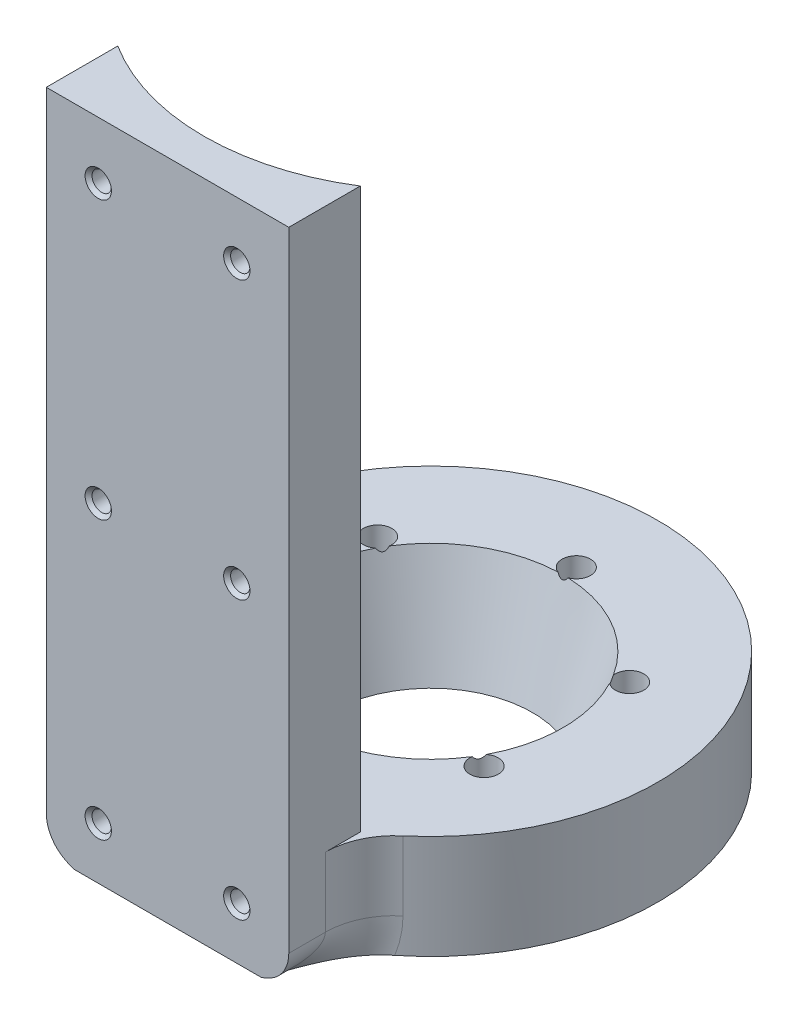
SolidWorks part; units mm, degrees
ref_plane "Front Plane" through (0, 0, 0) normal (0, 0, 1) x (1, 0, 0)
ref_plane "Top Plane" through (0, 0, 0) normal (0, 1, 0) x (1, 0, 0)
ref_plane "Right Plane" through (0, 0, 0) normal (1, 0, 0) x (0, 0, -1)
sketch "Sketch1" plane through (0, 0, 0) normal (0, 1, 0) x (1, 0, 0)
  circle A2 centre (0, 0) radius 32.75
  dimension "D1" = 65.5
extrude "Boss-Extrude1" add sketch "Sketch1" along normal mid plane 15
sketch "Sketch21" plane through (0, 0, 0) normal (1, 0, 0) x (0, 0, -1)
  line L0 (0, 7.5) -> (-19.1, 7.5)
  line L1 (32.75, 7.5) -> (-32.75, 7.5) construction
  line L2 (-19.1, 7.5) -> (-14.1, -9.5)
  line L3 (-14.1, -9.5) -> (0, -9.5)
  line L4 (0, -9.5) -> (0, 7.5)
  dimension "D1" = 19.1
  dimension "D2" = 14.1
  dimension "D3" = 17
revolve "Cut-Revolve1" cut sketch "Sketch21" angle 360 about L4
sketch "Sketch3" plane through (0, 7.5, 0) normal (0, 1, 0) x (1, 0, 0)
  line L1 (0, -1000) -> (0, 49000) construction
  circle A0 centre (0, 21) radius 2.05
  dimension "D1" = 4.1
  dimension "D2" = 21
extrude "Cut-Extrude2" cut sketch "Sketch3" against normal through all
pattern_circular "CirPattern1" count 6 over 360 about axis through (0, -7.5, 0) along (0, -1, 0) of "Cut-Extrude2"
sketch "Sketch11" plane through (0, 0, 0) normal (0, 0, 1) x (1, 0, 0)
  line L0 (-32.75, -7.5) -> (32.75, -7.5) construction
  line L1 (-12.5, -7.5) -> (12.5, -7.5)
  line L2 (-17.5, -2.5) -> (-17.5, 88.25)
  line L3 (-17.5, 88.25) -> (17.5, 88.25)
  line L4 (17.5, -2.5) -> (17.5, 88.25)
  line L5 (-17.5, -7.5) -> (17.5, 88.25) construction
  line L6 (-17.5, 88.25) -> (17.5, -7.5) construction
  line L7 (0, -1000) -> (0, 49000) construction
  arc A2 (17.5, -2.5) -> (12.5, -7.5) centre (12.5, -2.5) cw
  arc A3 (-12.5, -7.5) -> (-17.5, -2.5) centre (-12.5, -2.5) cw
  point P0 (0, 40.375)
  dimension "D2" = 5
  dimension "D1" = 35
  dimension "D3" = 95.75
extrude "Boss-Extrude2" add sketch "Sketch11" along normal blind 11 from offset 27
sketch "Sketch9" plane through (0, 0, 38) normal (0, 0, 1) x (1, 0, 0)
  line L0 (-12.5, -7.5) -> (12.5, -7.5) construction
  line L1 (-10, 0) -> (10, 0) construction
  line L2 (-10, 0) -> (-10, 80) construction
  line L3 (-10, 80) -> (10, 80) construction
  line L4 (10, 0) -> (10, 80) construction
  line L5 (-10, 0) -> (10, 80) construction
  line L6 (-10, 80) -> (10, 0) construction
  line L10 (0, -1000) -> (0, 49000) construction
  circle A0 centre (-10, 0) radius 1.4
  circle A1 centre (10, 0) radius 1.4
  circle A2 centre (10, 80) radius 1.4
  circle A3 centre (-10, 80) radius 1.4
  circle A4 centre (-10, 40) radius 1.4
  circle A5 centre (10, 40) radius 1.4
  point P1 (0, 40)
  point P3 (0, 40)
  dimension "D4" = 2.8
  dimension "D1" = 20
  dimension "D2" = 80
  dimension "D3" = 7.5
extrude "Cut-Extrude7" cut sketch "Sketch9" against normal blind 16
sketch "Sketch17" plane through (0, 88.25, 0) normal (0, 1, 0) x (1, 0, 0)
  circle A0 centre (0, 0) radius 32.75
  arc A1 (17.5, -27.6823) -> (-17.5, -27.6823) centre (0, 0) ccw construction
extrude "Cut-Extrude12" cut sketch "Sketch17" against normal up to surface (80.75 mm away) up to face at (0, 7.5, 0)
fillet "Fillet8" radius 10 4 edges at (15.8514, -6.2105, 28.6583) (-17.5, 2.5, 27.6823) (17.5, 2.5, 27.6823) (-8.9971, 1.0678, 31.4899)
chamfer "Chamfer1" distance 0.5 angle 45 6 edges at (11.4, 80, 38) (-8.6, 80, 38) (11.4, 0, 38) (-8.6, 0, 38) (11.4, 40, 38) (-8.6, 40, 38)
